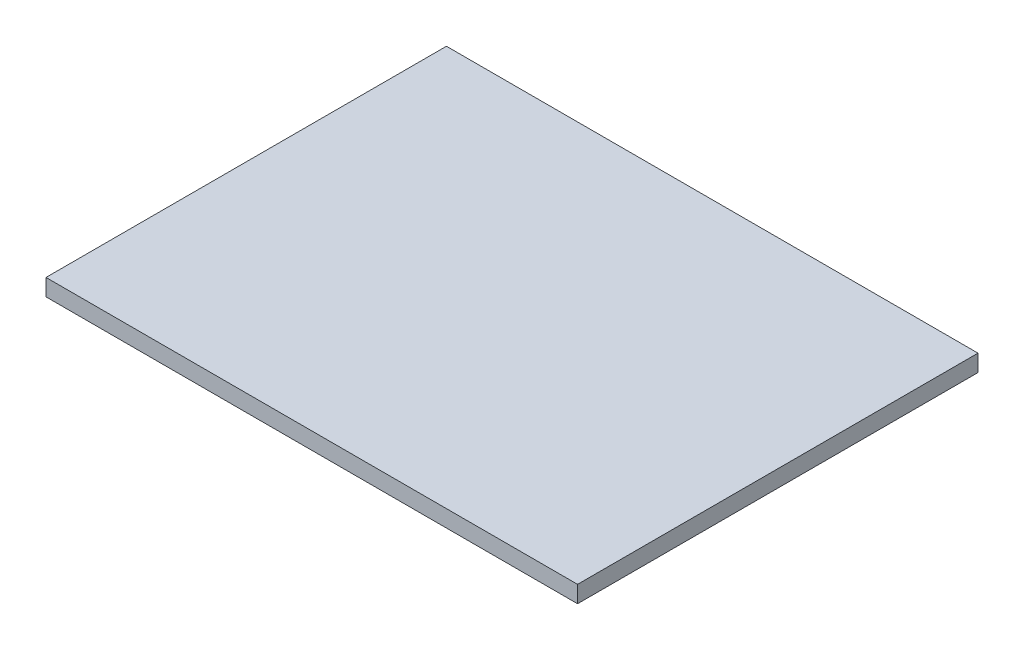
SolidWorks part; units mm, degrees
ref_plane "前视基准面" through (0, 0, 0) normal (0, 0, 1) x (1, 0, 0)
ref_plane "上视基准面" through (0, 0, 0) normal (0, 1, 0) x (1, 0, 0)
ref_plane "右视基准面" through (0, 0, 0) normal (1, 0, 0) x (0, 0, -1)
sketch "草图2" plane through (0, 0, 0) normal (0, 1, 0) x (1, 0, 0)
  line L1 (150, 113) -> (-150, 113)
  line L2 (150, 113) -> (150, -113)
  line L3 (150, -113) -> (-150, -113)
  line L4 (-150, 113) -> (-150, -113)
  line L5 (150, 113) -> (-150, -113) construction
  line L6 (150, -113) -> (-150, 113) construction
  point P0 (0, 0)
  dimension "D1" = 226
  dimension "D2" = 300
extrude "凸台-拉伸1" add sketch "草图2" along normal blind 9.5
sketch "草图3" plane through (0, 9.5, 0) normal (0, 1, 0) x (1, 0, 0)
  line L0 (-150, 0) -> (150, 0) construction
  line L1 (-150, 113) -> (-150, -113) construction
  line L2 (150, -113) -> (150, 113) construction
ref_plane "基准面1" through (0, 0, 0) normal (0, 0, -1) x (-1, 0, 0)
